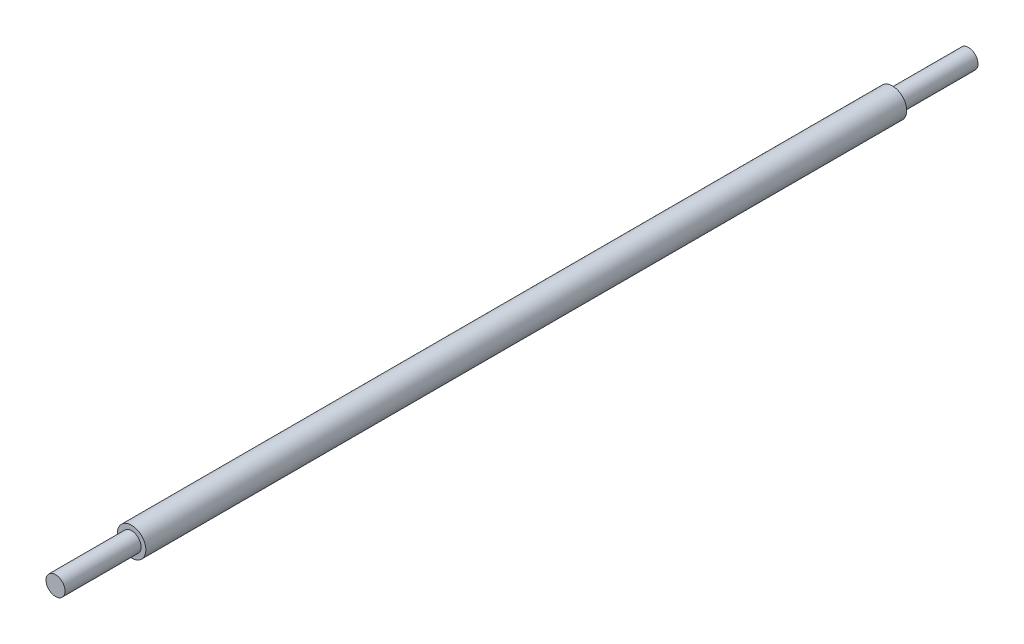
SolidWorks part; units mm, degrees
ref_plane "Front Plane" through (0, 0, 0) normal (0, 0, 1) x (1, 0, 0)
ref_plane "Top Plane" through (0, 0, 0) normal (0, 1, 0) x (1, 0, 0)
ref_plane "Right Plane" through (0, 0, 0) normal (1, 0, 0) x (0, 0, -1)
sketch "Sketch1" plane through (0, 0, 0) normal (0, 0, 1) x (1, 0, 0)
  circle A0 centre (0, 0) radius 2.3813
  dimension "D1" = 4.7625
extrude "Boss-Extrude1" add sketch "Sketch1" along normal blind 152.4
sketch "Sketch2" plane through (0, 0, 0) normal (0, 0, -1) x (-1, 0, 0)
  circle A0 centre (0, 0) radius 1.5875
  circle A1 centre (0, 0) radius 2.3813
  dimension "D1" = 3.175
extrude "Cut-Extrude1" cut sketch "Sketch2" against normal blind 12.7
sketch "Sketch3" plane through (0, 0, 152.4) normal (0, 0, 1) x (1, 0, 0)
  circle A0 centre (0, 0) radius 1.5875
  circle A1 centre (0, 0) radius 2.3813
  dimension "D1" = 3.175
extrude "Cut-Extrude2" cut sketch "Sketch3" against normal blind 12.7
